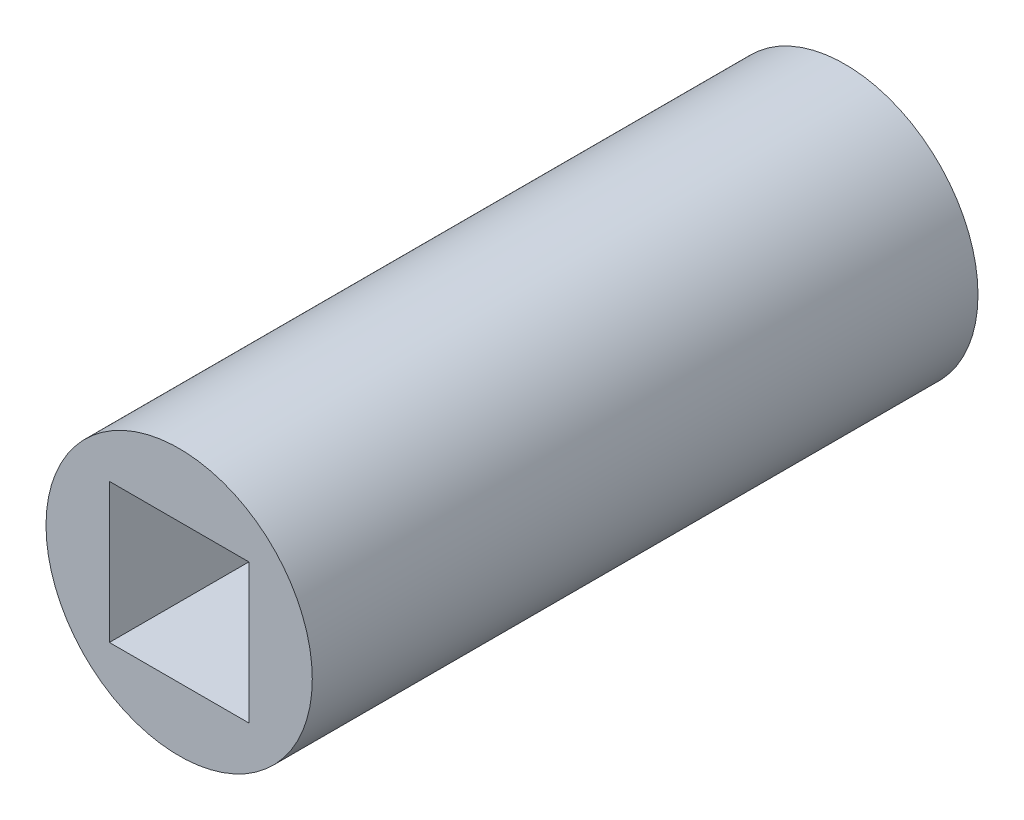
SolidWorks part; units mm, degrees
ref_plane "Front Plane" through (0, 0, 0) normal (0, 0, 1) x (1, 0, 0)
ref_plane "Top Plane" through (0, 0, 0) normal (0, 1, 0) x (1, 0, 0)
ref_plane "Right Plane" through (0, 0, 0) normal (1, 0, 0) x (0, 0, -1)
sketch "Sketch1" plane through (0, 0, 0) normal (0, 0, 1) x (1, 0, 0)
  line L0 (-2, 1.5) -> (2, 1.5)
  line L2 (-2.4495, 2.5) -> (2.4495, 2.5) construction
  arc A0 (-2, 1.5) -> (2, 1.5) centre (0, 0) ccw
  arc A1 (-2.4495, 2.5) -> (2.4495, 2.5) centre (0, 0) ccw
  arc A2 (-2.4495, 2.5) -> (2.4495, 2.5) centre (0, 0) cw
  dimension "D1" = 5
  dimension "D4" = 3.5
  dimension "D2" = 4
  dimension "D3" = 1
extrude "Boss-Extrude1" add sketch "Sketch1" along normal blind 10
sketch "Sketch2" plane through (0, 0, 10) normal (0, 0, 1) x (1, 0, 0)
  circle A0 centre (0, 0) radius 3.5
  dimension "D1" = 7
extrude "Boss-Extrude2" add sketch "Sketch2" along normal blind 7.5 contours A0
sketch "Sketch3" plane through (0, 0, 17.5) normal (0, 0, 1) x (1, 0, 0)
  line L1 (-1.8338, -1.8338) -> (1.8338, -1.8338)
  line L2 (-1.8338, -1.8338) -> (-1.8338, 1.8338)
  line L3 (-1.8338, 1.8338) -> (1.8338, 1.8338)
  line L4 (1.8338, -1.8338) -> (1.8338, 1.8338)
  line L5 (-1.8338, -1.8338) -> (1.8338, 1.8338) construction
  line L6 (-1.8338, 1.8338) -> (1.8338, -1.8338) construction
  point P0 (0, 0)
  dimension "D1" = 3.6676
  dimension "D2" = 3.6676
extrude "Cut-Extrude1" cut sketch "Sketch3" against normal blind 5
ref_axis "Axis1" through (0, 0, 17.7946) along (0, 0, -1)
